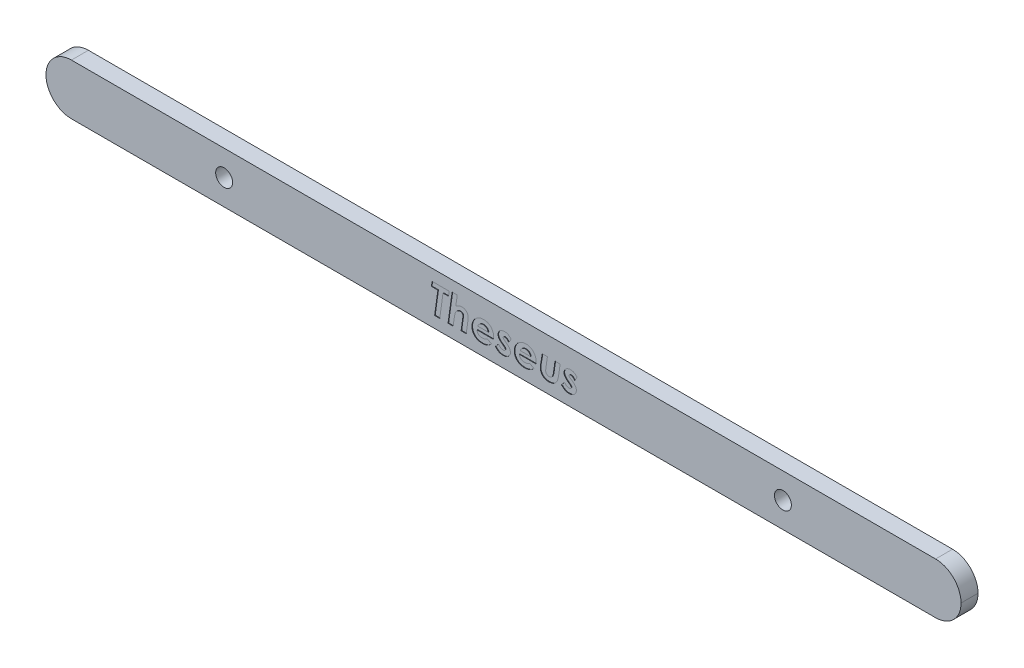
SolidWorks part; units mm, degrees
material "Acrylic (Medium-high impact)"
ref_plane "Front Plane" through (0, 0, 0) normal (0, 0, 1) x (1, 0, 0)
ref_plane "Top Plane" through (0, 0, 0) normal (0, 1, 0) x (1, 0, 0)
ref_plane "Right Plane" through (0, 0, 0) normal (1, 0, 0) x (0, 0, -1)
sketch "Sketch1" plane through (0, 0, 0) normal (0, 0, 1) x (1, 0, 0)
  line L0 (0, -1.65) -> (0, 1.65) construction
  line L1 (-80.9, 4.5) -> (80.9, 4.5)
  line L2 (-80.9, 4.5) -> (-80.9, -4.5)
  line L3 (-80.9, -4.5) -> (80.9, -4.5)
  line L4 (80.9, 4.5) -> (80.9, -4.5)
  circle A0 centre (-49.4, 0) radius 1.5
  circle A1 centre (49.4, 0) radius 1.5
  point P4 (0, 4.5)
  point P6 (-80.9, 0)
  dimension "D3" = 3
  dimension "D4" = 30
  dimension "D2" = 98.8
  dimension "D5" = 3
  dimension "D1" = 9
extrude "Boss-Extrude1" add sketch "Sketch1" along normal mid plane 3
sketch "Sketch2" plane through (0, 0, 1.5) normal (0, 0, 1) x (1, 0, 0)
  line L0 (-35.6678, -2.5) -> (35.6678, -2.5) construction
  line L2 (-80.9, -4.5) -> (80.9, -4.5) construction
  text T0 "<b><i>Theseus</i></b>" font "Century Gothic" height 5
  point P5 (0, 0)
  point P7 (0, -2.5)
  dimension "D1" = 2
extrude "Cut-Extrude1" cut sketch "Sketch2" against normal blind 0.1
fillet "Fillet1" radius 4.5 4 edges at (80.9, -4.5, 0) (80.9, 4.5, 0) (-80.9, -4.5, 0) (-80.9, 4.5, 0)
